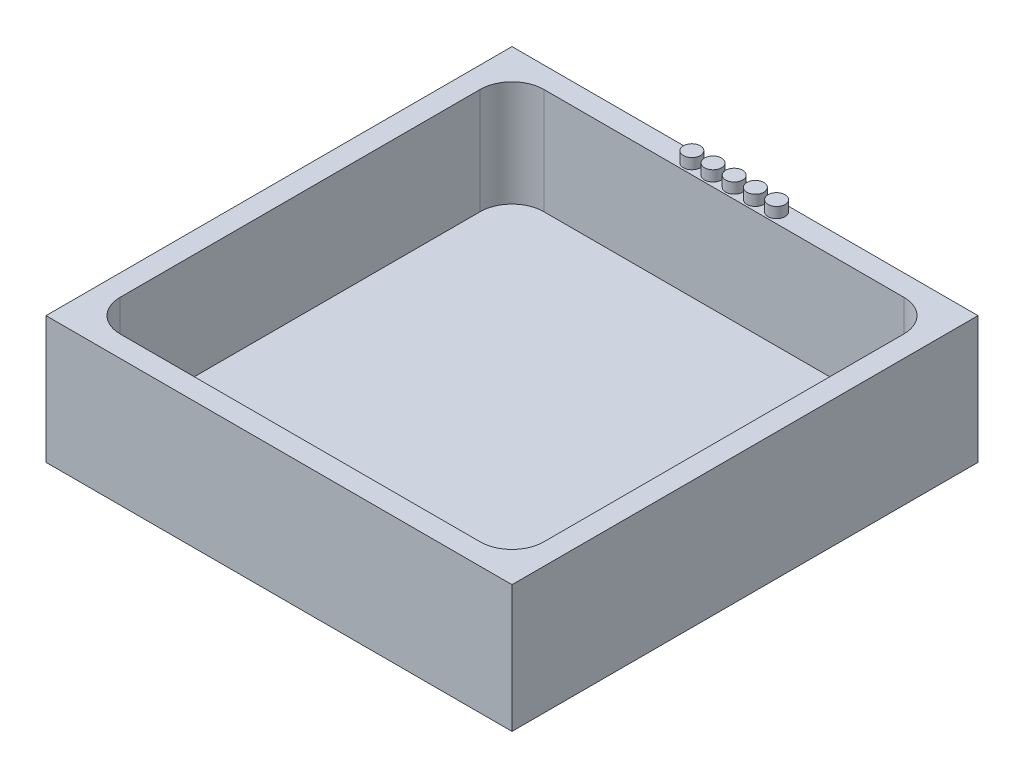
SolidWorks part; units mm, degrees
ref_plane "Front Plane" through (0, 0, 0) normal (0, 0, 1) x (1, 0, 0)
ref_plane "Top Plane" through (0, 0, 0) normal (0, 1, 0) x (1, 0, 0)
ref_plane "Right Plane" through (0, 0, 0) normal (1, 0, 0) x (0, 0, -1)
sketch "Sketch1" plane through (0, 0, 0) normal (0, 1, 0) x (1, 0, 0)
  line L1 (-10, -10) -> (10, -10)
  line L2 (-10, -10) -> (-10, 10)
  line L3 (-10, 10) -> (10, 10)
  line L4 (10, -10) -> (10, 10)
  line L5 (-10, -10) -> (10, 10) construction
  line L6 (-10, 10) -> (10, -10) construction
  line L7 (-11, -11) -> (11, -11)
  line L8 (-11, -11) -> (-11, 11)
  line L9 (-11, 11) -> (11, 11)
  line L10 (11, -11) -> (11, 11)
  line L11 (-11, -11) -> (11, 11) construction
  line L12 (-11, 11) -> (11, -11) construction
  point P0 (0, 0)
  point P6 (0, 0)
  dimension "D1" = 20
  dimension "D2" = 20
  dimension "D3" = 22
  dimension "D4" = 22
extrude "Boss-Extrude2" add sketch "Sketch1" along normal blind 1 contours L3 L4 L1 L2
extrude "Boss-Extrude3" add sketch "Sketch1<6>" along normal blind 6
sketch "Sketch1<6>" plane through (0, 0, 0) normal (0, 1, 0) x (1, 0, 0) same geometry as "Sketch1"
sketch "Sketch2" plane through (0, 6, 0) normal (0, 1, 0) x (1, 0, 0)
  line L0 (0, -3.3) -> (0, 3.3) construction
  circle A0 centre (0, 10.4902) radius 0.4
  circle A1 centre (1, 10.4902) radius 0.4
  circle A2 centre (-1, 10.4902) radius 0.4
  circle A3 centre (-2, 10.4902) radius 0.4
  circle A4 centre (2, 10.4902) radius 0.4
  dimension "D1" = 1
  dimension "D3" = 1
  dimension "D2" = 1
  dimension "D4" = 1
extrude "Boss-Extrude4" add sketch "Sketch2" along normal blind 0.5
fillet "Fillet1" radius 1.5 4 edges at (10, 3.5, -10) (-10, 3.5, -10) (-10, 3.5, 10) (10, 3.5, 10)
